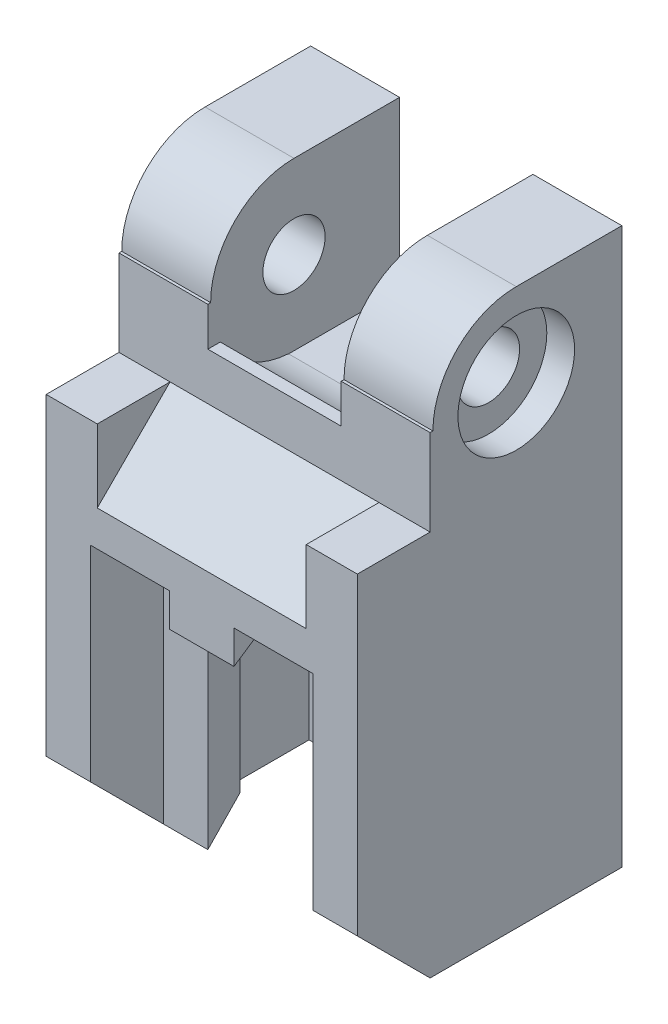
SolidWorks part; units mm, degrees
material "Plastique personnalisé"
ref_plane "前视基准面" through (0, 0, 0) normal (0, 0, 1) x (1, 0, 0)
ref_plane "上视基准面" through (0, 0, 0) normal (0, 1, 0) x (1, 0, 0)
ref_plane "右视基准面" through (0, 0, 0) normal (1, 0, 0) x (0, 0, -1)
sketch "Sketch1" plane through (0, 0, 0) normal (0, 1, 0) x (1, 0, 0)
  line L1 (-13, 14) -> (13, 14)
  line L2 (-13, 14) -> (-13, -14)
  line L3 (-13, -14) -> (13, -14)
  line L4 (13, 14) -> (13, -14)
  line L5 (-13, 14) -> (13, -14) construction
  line L6 (-13, -14) -> (13, 14) construction
  point P0 (0, 0)
  dimension "D1" = 26
  dimension "D2" = 28
extrude "Boss-Extrude1" add sketch "Sketch1" along normal blind 50
sketch "Sketch3" plane through (0, 0, 0) normal (0, 1, 0) x (1, 0, 0)
  line L0 (9.999, 2.65) -> (9.999, 9.85)
  line L1 (9.999, 9.85) -> (2.9003, 9.85)
  line L2 (-10, 9.85) -> (-10, 2.65)
  line L3 (-2.9, 9.85) -> (-10, 9.85)
  line L4 (-10, -3.25) -> (-10, -4.35)
  line L5 (6.0729, -3.25) -> (10.0625, -3.25)
  line L7 (13, 14) -> (-13, 14) construction
  line L8 (10.19, -15.102) -> (-10, -15.0895)
  line L9 (2.9003, 9.85) -> (2.8812, 5.8228)
  line L10 (13, -14) -> (13, 14) construction
  line L11 (-10, -3.25) -> (-6, -3.25)
  line L12 (2.8812, 5.8228) -> (-2.9188, 5.85)
  line L14 (-10, 2.65) -> (-9, 2.65)
  line L15 (9.999, 2.65) -> (8.999, 2.65)
  line L16 (-6, -3.25) -> (-9, 2.65)
  line L17 (6.0729, -3.25) -> (8.999, 2.65)
  line L22 (-10, -3.25) -> (-6, -3.25)
  line L31 (10.1233, -8.8993) -> (10.19, -15.102)
  line L38 (-2.9, 9.85) -> (-2.9188, 5.85)
  line L47 (-10, -4.35) -> (-10, -15.0895)
  line L53 (10.0689, -3.8496) -> (10.0625, -3.2497)
  line L55 (10.1233, -8.8993) -> (10.0689, -3.8496)
  point P38 (10, 3.3)
  point P94 (-3.25, -9.8)
  point P121 (3.25, -9.8)
  dimension "D3" = 7.1
  dimension "D4" = 5.8
  dimension "D5" = 0
  dimension "D6" = 5.9
  dimension "D2" = 1
  dimension "D8" = 5.9
  dimension "D9" = 7.2
  dimension "D10" = 7.2
  dimension "D12" = 4.15
extrude "Cut-Extrude6" cut sketch "Sketch3" along normal blind 25 contours L9 L1 L55 L31 L8 L47 L22 region at (0.038, 0, 3.3058)
sketch "Sketch7" plane through (13, 0, 0) normal (1, 0, 0) x (0, 0, -1)
  line L0 (4.5, 50) -> (-14, 50)
  line L1 (-14, 50) -> (-14, 24)
  line L2 (-14, 50) -> (-14, 0) construction
  line L3 (-14, 24) -> (-0.8033, 37.1967)
  line L4 (7.5, 35.3637) -> (14, 50) construction
  line L6 (14, 50) -> (14, 0) construction
  line L7 (14, 42.5) -> (4.5, 42.5) construction
  arc A0 (-0.8033, 37.1967) -> (4.5, 50) centre (4.5, 42.5) ccw
  dimension "D2" = 7.5
  dimension "D5" = 15
  dimension "D1" = 26
  dimension "D3" = 9.5
  dimension "D4" = 45
extrude "Cut-Extrude3" cut sketch "Sketch7" against normal blind 39
sketch "Sketch14" plane through (13, 0, 0) normal (1, 0, 0) x (0, 0, -1)
  line L0 (14, 50) -> (14, 0) construction
  circle A0 centre (4.5, 42.5) radius 7.5
  dimension "D1" = 9.5
extrude "Boss-Extrude7" add sketch "Sketch14" against normal blind 7
mirror "Symétrie1" about plane through (0, 0, 0) normal (1, 0, 0) of "Boss-Extrude7"
sketch "Sketch15" plane through (13, 0, 0) normal (1, 0, 0) x (0, 0, -1)
  line L0 (14, 50) -> (14, 0) construction
  line L1 (4.5, 42.5) -> (1.6109, 40.6109) construction
  line L2 (4.5, 50) -> (14, 50) construction
  circle A1 centre (4.5, 42.5) radius 2.8
  dimension "D1" = 5.6
  dimension "D2" = 9.5
  dimension "D3" = 7.5
extrude "Cut-Extrude4" cut sketch "Sketch15" against normal blind 28
sketch "Sketch16" plane through (13, 0, 0) normal (1, 0, 0) x (0, 0, -1)
  circle A0 centre (4.5, 42.5) radius 5.25
  dimension "D1" = 10.5
extrude "Cut-Extrude5" cut sketch "Sketch16" against normal blind 1.5
mirror "Mirror3" about plane through (0, 0, 0) normal (1, 0, 0) of "Cut-Extrude5"
sketch "Sketch17" plane through (0, 0, 0) normal (0, -1, 0) x (1, 0, 0)
  line L0 (-9.3, 3.25) -> (-13, 3.25)
  line L2 (9.3, 3.25) -> (9.3, 9.8)
  line L3 (-13, -14) -> (-13, 14) construction
  line L4 (-13, 3.25) -> (-13, 14)
  line L5 (-9.3, 3.25) -> (-9.3, 9.8)
  line L6 (-13, 14) -> (13, 14)
  line L8 (13, 14) -> (13, 3.25)
  line L9 (13, 14) -> (13, -14) construction
  line L10 (13, 3.25) -> (9.3, 3.25)
  line L14 (9.3, 9.8) -> (-9.3, 9.8)
extrude "Cut-Extrude7" cut sketch "Sketch17" against normal through all
sketch "Sketch19" plane through (0, 0, -14) normal (0, 0, -1) x (-1, 0, 0)
  line L0 (-13, 0) -> (13, 0) construction
  circle A0 centre (0, 15) radius 2.15
  point P2 (0, 0)
  dimension "D1" = 4.3
  dimension "D2" = 15
extrude "Cut-Extrude9" cut sketch "Sketch19" against normal blind 50
sketch "Sketch20" plane through (0, 0, -14) normal (0, 0, -1) x (-1, 0, 0)
  circle A0 centre (0, 15) radius 4
  dimension "D1" = 8
extrude "Cut-Extrude10" [suppressed] cut sketch "Sketch20" against normal blind 3
sketch "Esquisse1" plane through (0, 50, 0) normal (0, 1, 0) x (1, 0, 0)
  line L0 (13, 14) -> (-13, 14) construction
  line L1 (6, 4.5) -> (-6, 4.5)
  line L2 (6, 4.5) -> (6, 14)
  line L3 (6, 14) -> (-6, 14)
  line L4 (-6, 4.5) -> (-6, 14)
  dimension "D1" = 12
extrude "Enlèv. mat.-Extru.1" cut sketch "Esquisse1" against normal blind 7.5
sketch "Esquisse2" plane through (-13, 0, 0) normal (-1, 0, 0) x (0, 0, 1)
  line L0 (3.25, 0) -> (-14, 0) construction
  line L3 (-14, 50) -> (-14, 0) construction
  circle A0 centre (-8, 14.2) radius 1.7
  circle A1 centre (-3, 5.2) radius 1.7
  dimension "D5" = 3.4
  dimension "D6" = 3.4
  dimension "D1" = 5.2
  dimension "D2" = 14.2
  dimension "D3" = 6
  dimension "D4" = 11
extrude "Enlèv. mat.-Extru.2" [suppressed] cut sketch "Esquisse2" against normal blind 7.5
mirror "Symétrie2" [suppressed] about plane through (0, 0, 0) normal (1, 0, 0)
sketch "Esquisse3" plane through (0, 0, -14) normal (0, 0, -1) x (-1, 0, 0)
  line L1 (6, 42.5) -> (-6, 42.5)
  line L2 (6, 42.5) -> (6, 35)
  line L3 (6, 35) -> (-6, 35)
  line L4 (-6, 42.5) -> (-6, 35)
  dimension "D1" = 12
  dimension "D2" = 7.5
extrude "Enlèv. mat.-Extru.3" cut sketch "Esquisse3" against normal blind 10
sketch "Esquisse5" plane through (13, 0, 0) normal (1, 0, 0) x (0, 0, -1)
  line L1 (-3.25, 42.5) -> (-3, 42.5)
  arc A0 (4.5, 50) -> (-0.8033, 37.1967) centre (4.5, 42.5) ccw construction
chamfer "Chanfrein1" [suppressed] distance 1 angle 45
chamfer "Chanfrein2" [suppressed] distance 1 angle 45
sketch "Esquisse6" plane through (13, 0, 0) normal (1, 0, 0) x (0, 0, -1)
  line L0 (-3.25, 34.75) -> (-3.25, 42.5)
  line L1 (-3.25, 42.5) -> (-3, 42.5)
  line L2 (-3.25, 34.75) -> (-0.8033, 37.1967)
  arc A0 (-3, 42.5) -> (-0.8033, 37.1967) centre (4.5, 42.5) ccw
extrude "Boss.-Extru.1" add sketch "Esquisse6" against normal blind 26
sketch "Sketch18" plane through (0, 0, 0) normal (1, 0, 0) x (0, 0, -1)
  line L0 (-2.0267, 35.9733) -> (-2.0267, 31.9733)
  line L2 (-2.0267, 31.9733) -> (-6.0267, 31.9733)
  line L3 (-3.25, 34.75) -> (-6.0267, 31.9733)
  line L4 (-2.0267, 35.9733) -> (-3.25, 35.9733)
  line L6 (-3.25, 34.75) -> (-3.25, 35.9733)
  line L7 (-3.25, 42.5) -> (-3.25, 0) construction
  dimension "D1" = 4
  dimension "D2" = 4
extrude "Enlèv. mat.-Extru.4" [suppressed] cut sketch "Sketch18" against normal blind 3.45 and the other way blind 3.45
sketch "Esquisse7" plane through (0, 42.5, 0) normal (0, 1, 0) x (1, 0, 0)
  line L0 (6, 3.6159) -> (6, -7.0964)
  line L1 (6, -7.0964) -> (-6, -3.7801)
  line L2 (-6, -3.7801) -> (-6, 8.4569)
  line L4 (-6, 8.4569) -> (6, 3.6159)
extrude "Enlèv. mat.-Extru.5" cut sketch "Esquisse7" against normal blind 3.5
sketch "Esquisse8" plane through (0, 42.5, 0) normal (0, 1, 0) x (1, 0, 0)
sketch "Esquisse9" plane through (0, 25, 0) normal (0, -1, 0) x (-1, 0, 0)
  line L0 (9.3, -9.8) -> (-9.3, -9.8) construction
  line L1 (2.9, -9.8) -> (-2.9, -9.8)
  line L2 (2.9, -9.8) -> (2.9, -6.8)
  line L3 (2.9, -6.8) -> (-2.9, -6.8)
  line L4 (-2.9, -9.8) -> (-2.9, -6.8)
  line L5 (9.3, -3.25) -> (9.3, -9.8) construction
  dimension "D1" = 5.8
  dimension "D2" = 3
  dimension "D3" = 6.4
extrude "Boss.-Extru.3" add sketch "Esquisse9" along normal blind 1
sketch "Esquisse10" plane through (-2.9, 0, 0) normal (-1, 0, 0) x (0, 0, 1)
  line L0 (9.8, 24) -> (9.8, 22)
  line L1 (9.8, 22) -> (6.8, 24)
  line L2 (9.8, 24) -> (6.8, 24)
  dimension "D1" = 2
extrude "Boss.-Extru.4" add sketch "Esquisse10" against normal up to vertex (5.8 mm away) up to point (2.9, 24, 6.8)
sketch "Esquisse11" plane through (-9.3, 0, 0) normal (-1, 0, 0) x (0, 0, 1)
  line L0 (3.25, 34.75) -> (9.8, 28.2)
  line L2 (3.25, 34.75) -> (3.25, 25)
  line L3 (3.25, 25) -> (9.8, 25)
  line L4 (9.8, 28.2) -> (9.8, 25)
extrude "Boss.-Extru.5" add sketch "Esquisse11" along normal blind 0.1
sketch "Esquisse12" plane through (9.3, 0, 0) normal (1, 0, 0) x (0, 0, -1)
  line L0 (-9.8, 25) -> (-9.8, 28.2)
  line L1 (-9.8, 28.2) -> (-3.25, 34.75)
  line L2 (-3.25, 34.75) -> (-3.25, 25)
  line L3 (-3.25, 25) -> (-9.8, 25)
extrude "Boss.-Extru.6" add sketch "Esquisse12" along normal blind 0.1
sketch "Esquisse13" plane through (9.4, 0, 0) normal (1, 0, 0) x (0, 0, -1)
  line L1 (-3.25, 34.75) -> (-9.8, 34.75)
  line L2 (-3.25, 34.75) -> (-3.25, 25)
  line L3 (-3.25, 25) -> (-9.8, 25)
  line L4 (-9.8, 34.75) -> (-9.8, 25)
extrude "Boss.-Extru.7" add sketch "Esquisse13" along normal up to vertex (3.6 mm away) up to point (13, 42.5, 3.25)
sketch "Esquisse14" plane through (-9.4, 0, 0) normal (-1, 0, 0) x (0, 0, 1)
  line L1 (3.25, 34.75) -> (9.8, 34.75)
  line L2 (3.25, 34.75) -> (3.25, 25)
  line L3 (3.25, 25) -> (9.8, 25)
  line L4 (9.8, 34.75) -> (9.8, 25)
extrude "Boss.-Extru.8" add sketch "Esquisse14" along normal up to vertex (3.6 mm away) up to point (-13, 42.5, 3.25)
sketch "Esquisse16" plane through (-13, 0, 0) normal (-1, 0, 0) x (0, 0, 1)
  line L0 (3.25, 0) -> (-14, 0)
  line L1 (-14, 0) -> (-14, 50)
  line L2 (-14, 50) -> (-4.5, 50)
  line L4 (3, 42.5) -> (3.25, 42.5)
  line L5 (3.25, 42.5) -> (3.25, 34.75)
  line L6 (3.25, 34.75) -> (9.8, 34.75)
  line L7 (9.8, 34.75) -> (9.8, 25)
  line L8 (9.8, 25) -> (3.25, 25)
  line L9 (3.25, 25) -> (3.25, 0)
  circle A0 centre (-4.5, 42.5) radius 5.25
  arc A1 (-4.5, 50) -> (3, 42.5) centre (-4.5, 42.5) cw
extrude "Boss.-Extru.9" add sketch "Esquisse16" along normal blind 1
sketch "Esquisse17" plane through (13, 0, 0) normal (1, 0, 0) x (0, 0, -1)
  line L0 (-3, 42.5) -> (-3.25, 42.5)
  line L1 (-3.25, 42.5) -> (-3.25, 34.75)
  line L2 (-3.25, 34.75) -> (-9.8, 34.75)
  line L3 (-9.8, 34.75) -> (-9.8, 25)
  line L4 (-9.8, 25) -> (-3.25, 25)
  line L5 (-3.25, 25) -> (-3.25, 0)
  line L6 (-3.25, 0) -> (14, 0)
  line L7 (14, 0) -> (14, 50)
  line L8 (14, 50) -> (4.5, 50)
  arc A0 (4.5, 50) -> (-3, 42.5) centre (4.5, 42.5) ccw
  circle A1 centre (4.5, 42.5) radius 5.25
extrude "Boss.-Extru.10" add sketch "Esquisse17" along normal blind 1
sketch "Esquisse20" plane through (0, 0, 3.25) normal (0, 0, 1) x (1, 0, 0)
  line L0 (-14, 25) -> (-6, 25) construction
  line L1 (-14, 0) -> (-10, 0)
  line L2 (-14, 0) -> (-14, 25)
  line L3 (-14, 25) -> (-10, 25)
  line L4 (-10, 0) -> (-10, 25)
  line L5 (6.0729, 0) -> (14, 0) construction
  line L6 (14, 25) -> (10, 25)
  line L7 (14, 25) -> (14, 0)
  line L8 (14, 0) -> (10, 0)
  line L9 (10, 25) -> (10, 0)
  dimension "D1" = 4
  dimension "D2" = 4
extrude "Boss.-Extru.11" add sketch "Esquisse20" along normal up to vertex (6.55 mm away) up to point (-14, 25, 9.8)
sketch "Esquisse22" plane through (10, 0, 0) normal (-1, 0, 0) x (0, 0, 1)
  line L0 (3.25, 0) -> (9.8, 6.55)
  line L1 (9.8, 25) -> (9.8, 0) construction
  line L2 (9.8, 6.55) -> (13.1226, -3.8264)
  line L3 (13.1226, -3.8264) -> (3.25, -3.6168)
  line L4 (3.25, -3.6168) -> (3.25, 0)
  line L5 (9.8, 0) -> (3.25, 0) construction
  dimension "D1" = 45
extrude "Enlèv. mat.-Extru.6" cut sketch "Esquisse22" against normal blind 10 and the other way blind 34
